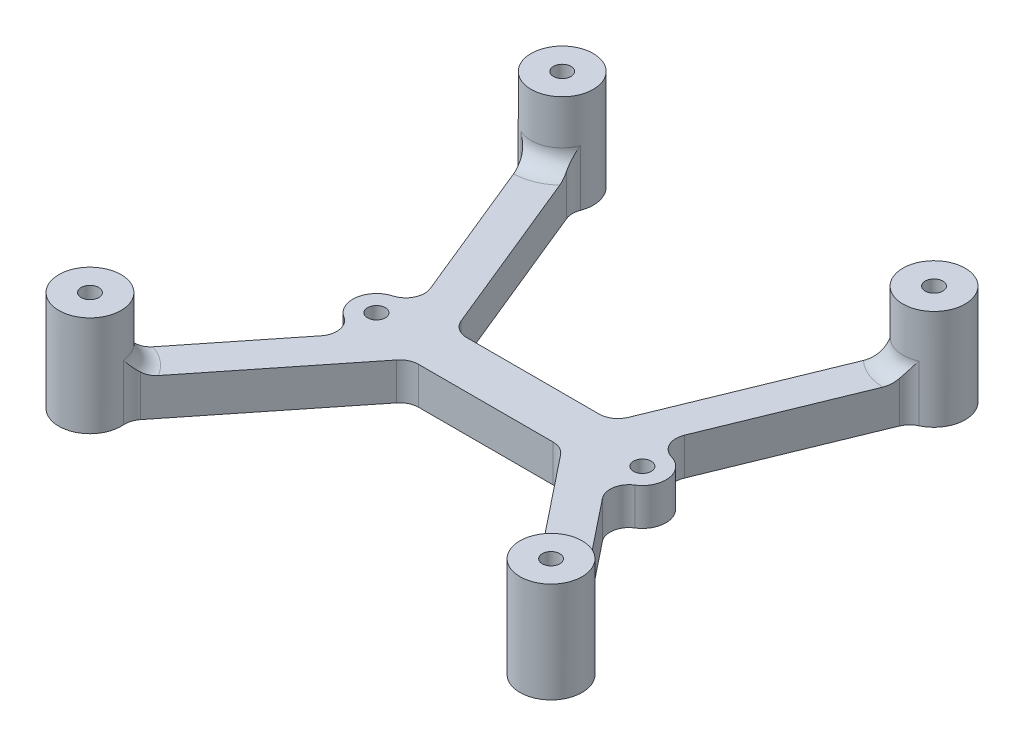
SolidWorks part; units mm, degrees
ref_plane "Front Plane" through (0, 0, 0) normal (0, 0, 1) x (1, 0, 0)
ref_plane "Top Plane" through (0, 0, 0) normal (0, 1, 0) x (1, 0, 0)
ref_plane "Right Plane" through (0, 0, 0) normal (1, 0, 0) x (0, 0, -1)
sketch "Sketch1" plane through (0, 0, 0) normal (0, 1, 0) x (1, 0, 0)
  line L0 (-17.875, 0) -> (17.875, 0) construction
  line L1 (-17.875, 0) -> (17.875, 0) construction
  line L2 (-17.875, 3.175) -> (17.875, 3.175)
  line L3 (-17.875, -3.175) -> (17.875, -3.175)
  circle A0 centre (-17.875, 0) radius 1.1938
  circle A1 centre (17.875, 0) radius 1.1938
  arc A2 (-17.875, 3.175) -> (-17.875, -3.175) centre (-17.875, 0) ccw
  arc A3 (17.875, -3.175) -> (17.875, 3.175) centre (17.875, 0) ccw
  point P3 (0, 0)
  point P5 (0, 0)
  dimension "D2" = 2.3876
  dimension "D3" = 3.175
  dimension "D1" = 35.75
extrude "Boss-Extrude1" add sketch "Sketch1" along normal blind 5
sketch "Sketch2" plane through (0, 0, 0) normal (0, 1, 0) x (1, 0, 0)
  line L0 (-31, -25.4) -> (0, -25.4) construction
  line L1 (0, -25.4) -> (0, 32.1) construction
  line L2 (0, 32.1) -> (-25, 32.1) construction
  circle A0 centre (-25, 32.1) radius 1.1811
  circle A1 centre (-25, 32.1) radius 4.1811
  circle A2 centre (-31, -25.4) radius 1.1811
  circle A3 centre (-31, -25.4) radius 4.1811
  dimension "D1" = 2.3622
  dimension "D2" = 3
  dimension "D4" = 57.5
  dimension "D3" = 31
  dimension "D5" = 25
  dimension "D6" = 25.4
extrude "Boss-Extrude2" add sketch "Sketch2" along normal blind 13.4937 separate body
sketch "Sketch4" plane through (0, 0, 0) normal (0, -1, 0) x (-1, 0, 0)
  line L0 (30.7218, -21.2282) -> (26.9963, -24.195)
  line L1 (30.7218, -21.2282) -> (11.2877, 3.175)
  line L2 (26.9963, -24.195) -> (7.5622, 0.2081)
  line L3 (11.2877, 3.175) -> (7.5622, 0.2081)
  line L4 (25.9031, 28.0176) -> (21.495, 29.8204)
  line L5 (25.9031, 28.0176) -> (13.1463, -3.175)
  line L6 (21.495, 29.8204) -> (8.7382, -1.3722)
  line L7 (13.1463, -3.175) -> (8.7382, -1.3722)
  line L8 (17.875, -3.175) -> (-17.875, -3.175) construction
  line L9 (-17.875, 3.175) -> (17.875, 3.175) construction
  circle A0 centre (31, -25.4) radius 4.1811 construction
  circle A1 centre (25, 32.1) radius 4.1811 construction
  arc A2 (17.875, -3.175) -> (17.875, 3.175) centre (17.875, 0) ccw construction
  circle M5 centre (31, -25.4) radius 4.1811
  dimension "D1" = 4.7625
  dimension "D2" = 4.7625
extrude "Boss-Extrude3" add sketch "Sketch4" against normal up to surface (5 mm away) contours L5 L7 L2 L1 M5 | L4 L6 L3 L1 L5 region at (-20.4357, 0, 12.196) region at (-18.1198, 0, -15.2019) up to face at (-17.875, 5, 1.1938)
fillet "Fillet1" radius 2.54 10 edges at (-10.2565, 2.5, 3.175) (-10.5978, 2.5, -3.175) (-15.7432, 2.5, -3.175) (-16.3447, 2.5, 3.175) (-30.7218, 2.5, 21.2282) (-28.3953, 5, 22.1293) (-23.4173, 5, -28.23) (-25.9031, 2.5, -28.0176) (-21.495, 2.5, -29.8204) (-26.9963, 2.5, 24.195)
mirror "Mirror7" about plane through (0, 0, 0) normal (1, 0, 0) of bodies 106
